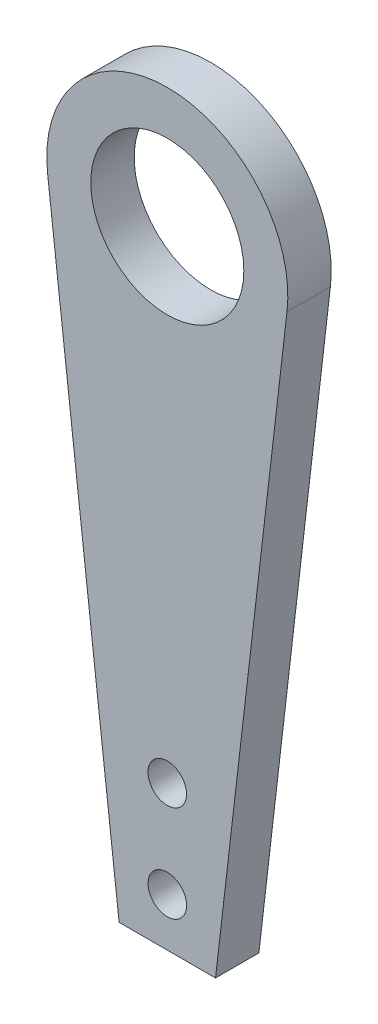
SolidWorks part; units mm, degrees
ref_plane "Front Plane" through (0, 0, 0) normal (0, 0, 1) x (1, 0, 0)
ref_plane "Top Plane" through (0, 0, 0) normal (0, 1, 0) x (1, 0, 0)
ref_plane "Right Plane" through (0, 0, 0) normal (1, 0, 0) x (0, 0, -1)
ref_axis "X Axis" through (-88.99, 0, 0) along (1, 0, 0)
ref_axis "Y Axiz" through (0, 0, 55) along (0, 0, -1)
ref_axis "Z Axis" through (0, 55, 0) along (0, -1, 0)
sketch "Sketch1" plane through (0, 0, 0) normal (0, 0, 1) x (1, 0, 0)
  line L0 (-5, -5) -> (5, -5)
  line L1 (-5, -5) -> (-12.4158, 58.5512)
  line L2 (0, -5) -> (0, 0) construction
  line L4 (12.4158, 58.5512) -> (5, -5)
  line L5 (0, 0) -> (0, 60) construction
  circle A0 centre (0, 0) radius 2
  circle A2 centre (0, 60) radius 7.9375
  arc A3 (12.4158, 58.5512) -> (-12.4158, 58.5512) centre (0, 60) ccw
  circle A4 centre (0, 10) radius 2
  dimension "D1" = 4
  dimension "D3" = 5
  dimension "D4" = 15.875
  dimension "D5" = 25
  dimension "D2" = 10
  dimension "D6" = 60
  dimension "D7" = 10
extrude "Boss-Extrude2" add sketch "Sketch1" along normal blind 4.5
